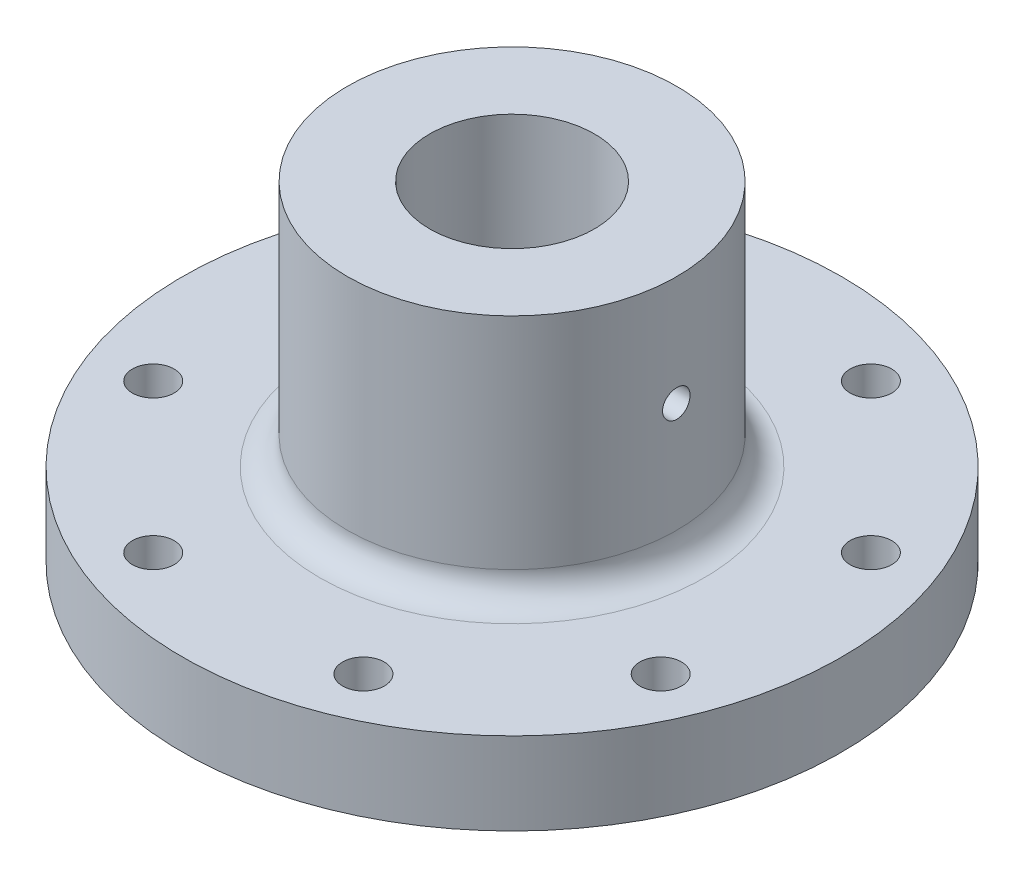
SolidWorks part; units mm, degrees
material "6061-T6 (SS)"
ref_plane "Front Plane" through (0, 0, 0) normal (0, 0, 1) x (1, 0, 0)
ref_plane "Top Plane" through (0, 0, 0) normal (0, 1, 0) x (1, 0, 0)
ref_plane "Right Plane" through (0, 0, 0) normal (1, 0, 0) x (0, 0, -1)
sketch "Sketch1" plane through (0, 0, 0) normal (0, 1, 0) x (1, 0, 0)
  circle A0 centre (0, 0) radius 38.1
  circle A1 centre (0, 0) radius 9.525
  dimension "D1" = 76.2
  dimension "D2" = 19.05
extrude "Boss-Extrude1" add sketch "Sketch1" along normal blind 38.1
hole_wizard "#10-32 Tapped Hole1" positions "Sketch3" profile "Sketch2" tap size "#10-32" standard "Ansi Inch" end condition through all
sketch "Sketch3" plane through (0, 38.1, 0) normal (0, 1, 0) x (-1, 0, 0)
  line L0 (38.1, 0) -> (0, 0) construction
  line L1 (0, 0) -> (29.3332, -12.1502) construction
  circle A0 centre (0, 0) radius 38.1 construction
  point P0 (29.3332, -12.1502)
  dimension "D1" = 31.75
  dimension "D2" = 22.5
sketch "Sketch2" plane through (-29.3332, 38.1, -12.1502) normal (1, 0, 0) x (0, 0, 1)
  line L0 (0, 0) -> (0, 38.1)
  line L1 (0, 38.1) -> (2.413, 38.1)
  line L2 (2.413, 38.1) -> (2.413, 0)
  line L5 (2.413, 0) -> (0, 0)
  line L11 (0, -6.35) -> (0, 107.95) construction
  dimension "Thread Major Dia." = 4.826
  dimension "Thru Tap Drill Depth" = 38.1
pattern_circular "CirPattern1" count 8 over 360 about axis through (0, 38.1, 0) along (0, -1, 0) of "#10-32 Tapped Hole1"
sketch "Sketch7" plane through (0, 38.1, 0) normal (0, 1, 0) x (1, 0, 0)
  circle A0 centre (0, 0) radius 19.05
  dimension "D1" = 38.1
extrude "Cut-Extrude2" cut sketch "Sketch7" against normal offset from surface (28.575 mm away) 9.525 flip side to cut up to face at (-29.3332, 0, 14.5632)
fillet "Fillet1" radius 3.175 1 edges at (0, 9.525, 19.05)
sketch "Sketch8" plane through (0, 0, 0) normal (1, 0, 0) x (0, 0, -1)
  line L0 (19.05, 38.1) -> (-19.05, 38.1) construction
  circle A0 centre (0, 25.4) radius 1.5875
  point P4 (3.8401, 25.4)
  dimension "D1" = 3.175
  dimension "D2" = 12.7
extrude "Cut-Extrude3" cut sketch "Sketch8" against normal through all both and the other way through all contours A0
